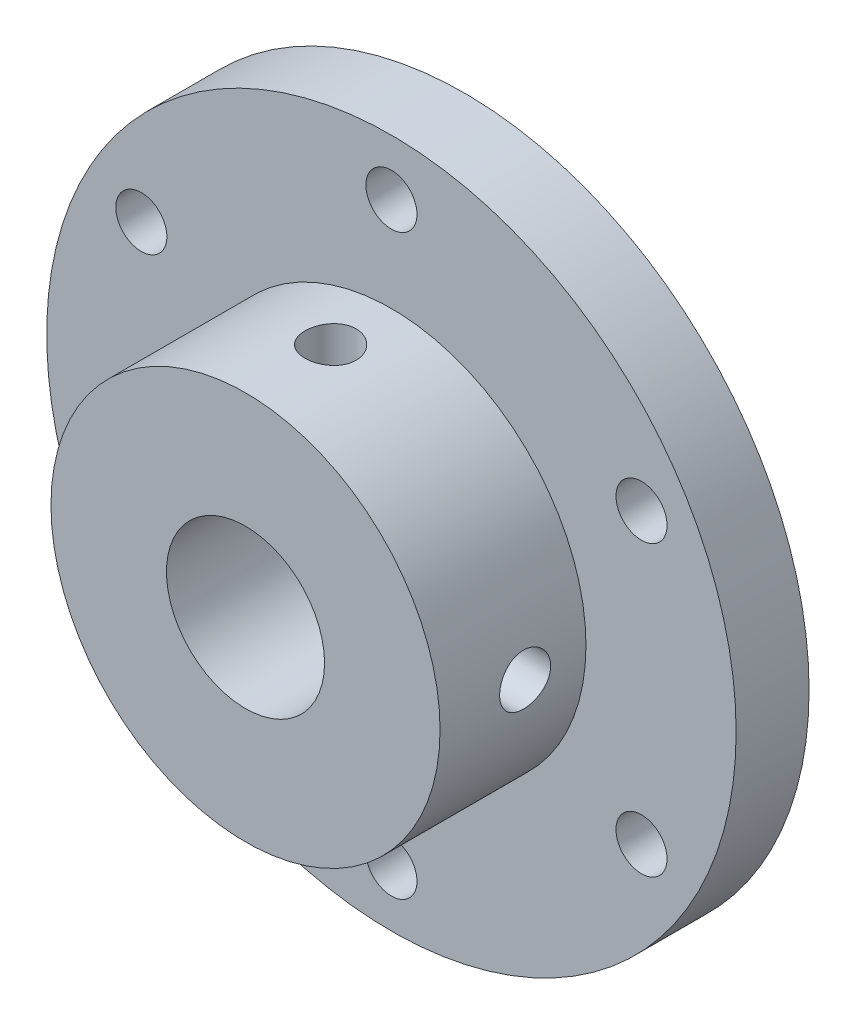
SolidWorks part; units mm, degrees
material "6061 合金"
ref_plane "前基準面" through (0, 0, 0) normal (0, 0, 1) x (1, 0, 0)
ref_plane "上基準面" through (0, 0, 0) normal (0, 1, 0) x (1, 0, 0)
ref_plane "右基準面" through (0, 0, 0) normal (1, 0, 0) x (0, 0, -1)
sketch "草圖1" plane through (0, 0, 0) normal (0, 0, 1) x (1, 0, 0)
  circle A0 centre (0, 0) radius 28.35
  dimension "D1" = 56.7
extrude "填料-伸長1" add sketch "草圖1" along normal blind 6
sketch "草圖2" plane through (0, 0, 6) normal (0, 0, 1) x (1, 0, 0)
  circle A0 centre (0, 0) radius 16
  dimension "D1" = 32
extrude "填料-伸長2" add sketch "草圖2" along normal blind 12
sketch "草圖3" plane through (0, 0, 18) normal (0, 0, 1) x (1, 0, 0)
  circle A0 centre (0, 0) radius 6.5
  dimension "D1" = 13
extrude "除料-伸長1" cut sketch "草圖3" against normal through all
hole_wizard "M5 螺紋孔2" positions "草圖7" profile "草圖8" tap size "M5" standard "ISO" end condition through all
sketch "草圖7" plane through (0, 0, 0) normal (0, 0, -1) x (-1, 0, 0)
  line L0 (0, 0) -> (0, 23.75) construction
  point P0 (0, 23.75)
  dimension "D1" = 23.75
sketch "草圖8" plane through (0, 23.75, 0) normal (1, 0, 0) x (0, 1, 0)
  line L0 (0, 0) -> (0, 18)
  line L1 (0, 18) -> (2.1, 18)
  line L2 (2.1, 18) -> (2.1, 0)
  line L5 (2.1, 0) -> (0, 0)
  line L11 (0, -6.35) -> (0, 107.95) construction
  dimension "貫穿螺孔鑽直徑" = 4.2
  dimension "貫穿螺孔鑽深度" = 18
pattern_circular "環狀複製排列1" count 6 over 360 about axis through (0, 0, 6) along (0, 0, 1) of "M5 螺紋孔2"
ref_plane "平面1" through (16, 0, 0) normal (1, 0, 0) x (0, 0, -1)
sketch "草圖6" plane through (16, 0, 0) normal (1, 0, 0) x (0, 0, -1)
  line L0 (-18, 0) -> (-6, 0) construction
  line L2 (-18, 16) -> (-18, -16) construction
  line L3 (-6, 28.35) -> (-6, -28.35) construction
  circle A0 centre (-11, 0) radius 2.1
  dimension "D2" = 4.2
  dimension "D1" = 5
extrude "除料-伸長3" cut sketch "草圖6" against normal up to next
ref_axis "基準軸1" through (6.0257, 0, 11) along (1, 0, 0)
pattern_circular "環狀複製排列2" count 2 over 90 about axis through (0, 0, 18) along (0, 0, 1) of "除料-伸長3"
